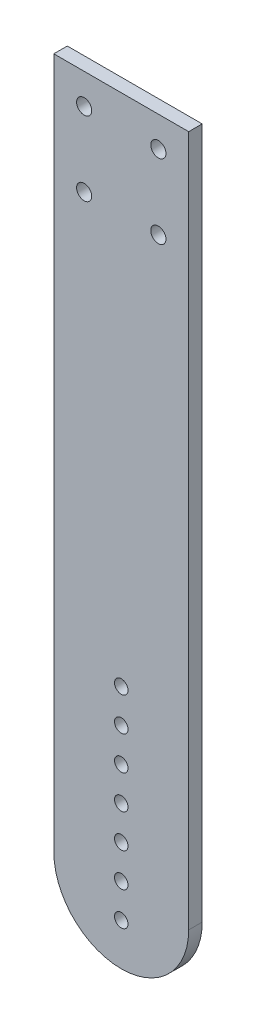
SolidWorks part; units mm, degrees
other "Markup1"
sketch "Sketch7" plane through (-20, 225, -2) normal (-0.1146, 0.1086, -0.9875) x (-0.991, 0.0573, 0.1213)
ref_plane "Front Plane" through (0, 0, 0) normal (0, 0, 1) x (1, 0, 0)
ref_plane "Top Plane" through (0, 0, 0) normal (0, 1, 0) x (1, 0, 0)
ref_plane "Right Plane" through (0, 0, 0) normal (1, 0, 0) x (0, 0, -1)
sketch "Sketch1" plane through (0, 0, 0) normal (0, 1, 0) x (1, 0, 0)
  line L1 (-20, 2) -> (20, 2)
  line L2 (-20, 2) -> (-20, -2)
  line L3 (-20, -2) -> (20, -2)
  line L4 (20, 2) -> (20, -2)
  line L5 (-20, 2) -> (20, -2) construction
  line L6 (-20, -2) -> (20, 2) construction
  point P0 (0, 0)
extrude "Boss-Extrude1" add sketch "Sketch1" along normal blind 225
fillet "Fillet1" radius 20 2 edges at (-20, 0, 0) (20, 0, 0)
sketch "Sketch2" plane through (0, 0, 2) normal (0, 0, 1) x (1, 0, 0)
  circle A0 centre (0, 12.5) radius 2
  dimension "D1" = 12.5
extrude "Cut-Extrude1" cut sketch "Sketch2" against normal through all
pattern_linear "LPattern1" count 7 spacing 10 along (0, 1, 0) of "Cut-Extrude1"
sketch "Sketch6" plane through (0, 0, -2) normal (0, 0, -1) x (-1, 0, 0)
  line L1 (-6.5, 1.0857) -> (-8.5, 1.0857)
  line L2 (-6.5, 1.0857) -> (-6.5, 101.0857)
  line L3 (-6.5, 101.0857) -> (-8.5, 101.0857)
  line L4 (-8.5, 1.0857) -> (-8.5, 101.0857)
  line L5 (-7.5, 101.0857) -> (-7.5, 1.0857) construction
  line L6 (-6.5, 51.0857) -> (-8.5, 51.0857) construction
  line L7 (-20, 225) -> (-20, 20) construction
  arc A0 (-20, 20) -> (0, 0) centre (0, 20) ccw construction
  point P524 (-7.5, 51.0857)
  dimension "D1" = 2
  dimension "D2" = 12.5
  dimension "D3" = 100
extrude "Cut-Extrude3" cut sketch "Sketch6" against normal blind 2 contours L3 L4 L1 L2
fillet "Fillet2" radius 1 2 edges at (8.5, 101.0857, -1) (6.5, 101.0857, -1)
mirror "Mirror1" about plane through (0, 0, 0) normal (1, 0, 0) of "Fillet2", "Cut-Extrude3"
sketch "Sketch8" plane through (0, 0, -2) normal (0, 0, -1) x (-1, 0, 0)
  line L0 (-20, 225) -> (20, 225) construction
  line L1 (-20, 225) -> (-20, 20) construction
  line L2 (20, 225) -> (20, 20) construction
  line L3 (-20, 185) -> (20, 185) construction
  circle A0 centre (-11, 216) radius 2.25
  circle A1 centre (11, 216) radius 2.25
  circle A2 centre (-11, 194) radius 2.25
  circle A3 centre (11, 194) radius 2.25
  point P16 (0, 0)
  point P17 (0, 0)
  point P18 (0, 0)
  point P19 (0, 0)
  dimension "D1" = 9
  dimension "D3" = 9
  dimension "D5" = 4.5
  dimension "D2" = 9
  dimension "D4" = 9
  dimension "D6" = 40
  dimension "D7" = 9
extrude "Cut-Extrude4" cut sketch "Sketch8" against normal through all
